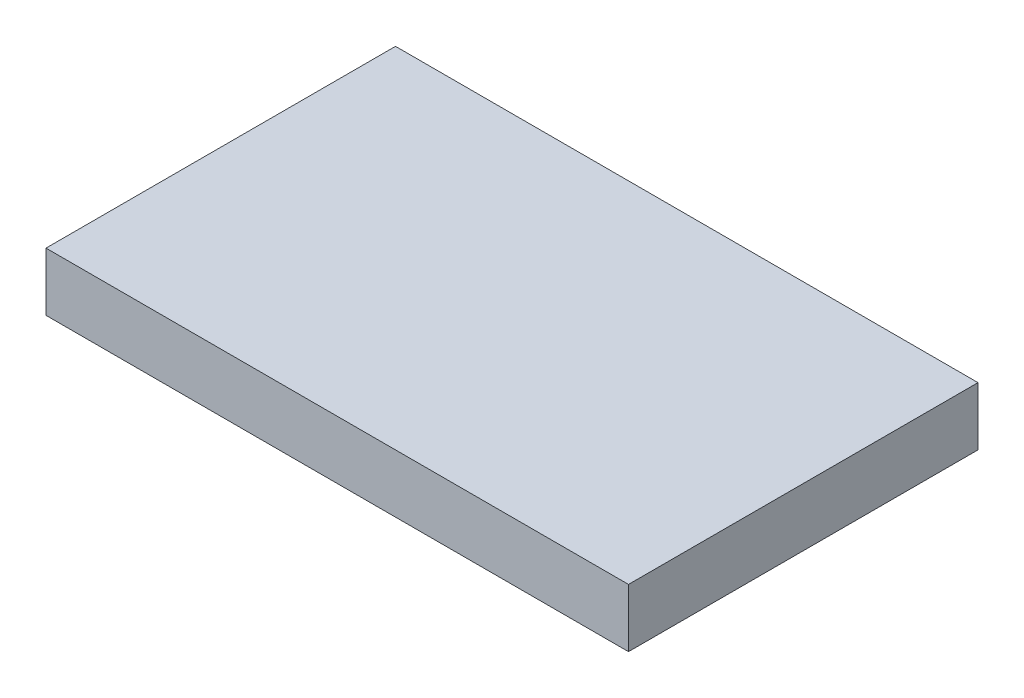
SolidWorks part; units mm, degrees
ref_plane "Front Plane" through (0, 0, 0) normal (0, 0, 1) x (1, 0, 0)
ref_plane "Top Plane" through (0, 0, 0) normal (0, 1, 0) x (1, 0, 0)
ref_plane "Right Plane" through (0, 0, 0) normal (1, 0, 0) x (0, 0, -1)
sketch "Sketch1" plane through (0, 0, 0) normal (0, 1, 0) x (1, 0, 0)
  line L1 (-63.5, -38.1) -> (63.5, -38.1)
  line L2 (-63.5, -38.1) -> (-63.5, 38.1)
  line L3 (-63.5, 38.1) -> (63.5, 38.1)
  line L4 (63.5, -38.1) -> (63.5, 38.1)
  line L5 (-63.5, -38.1) -> (63.5, 38.1) construction
  line L6 (-63.5, 38.1) -> (63.5, -38.1) construction
  point P0 (0, 0)
  dimension "D1" = 76.2
  dimension "D2" = 127
extrude "Boss-Extrude1" add sketch "Sketch1" along normal blind 12.7
